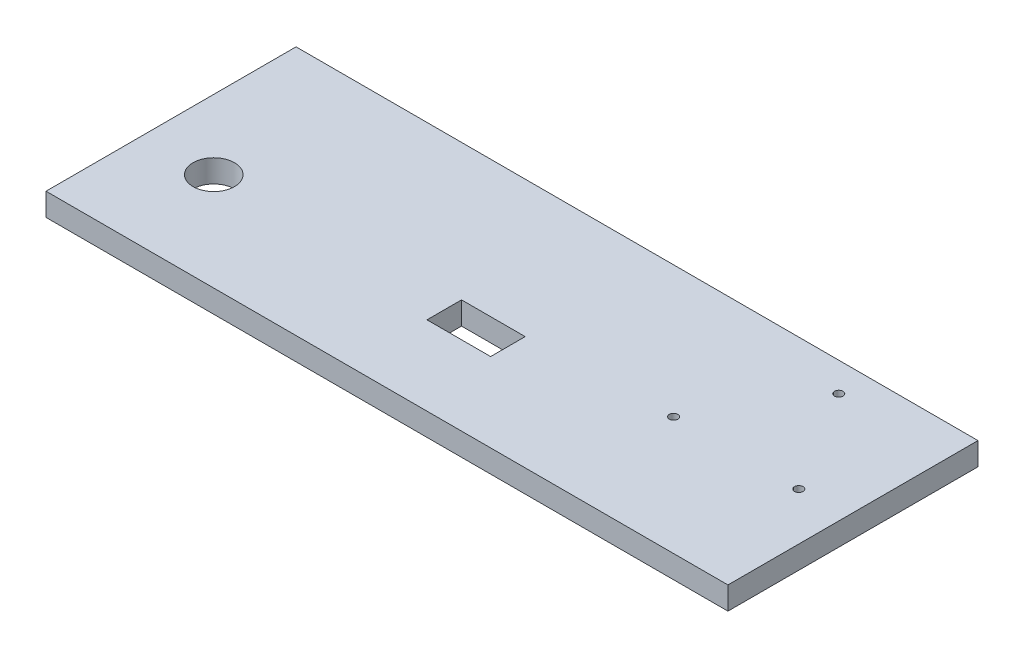
SolidWorks part; units mm, degrees
ref_plane "Front Plane" through (0, 0, 0) normal (0, 0, 1) x (1, 0, 0)
ref_plane "Top Plane" through (0, 0, 0) normal (0, 1, 0) x (1, 0, 0)
ref_plane "Right Plane" through (0, 0, 0) normal (1, 0, 0) x (0, 0, -1)
sketch "Sketch1" plane through (0, 0, 0) normal (0, 1, 0) x (1, 0, 0)
  line L1 (-47.625, -17.4625) -> (47.625, -17.4625)
  line L2 (-47.625, -17.4625) -> (-47.625, 17.4625)
  line L3 (-47.625, 17.4625) -> (47.625, 17.4625)
  line L4 (47.625, -17.4625) -> (47.625, 17.4625)
  line L5 (-47.625, -17.4625) -> (47.625, 17.4625) construction
  line L6 (-47.625, 17.4625) -> (47.625, -17.4625) construction
  point P0 (0, 0)
  dimension "D1" = 95.25
  dimension "D2" = 34.925
extrude "Boss-Extrude1" add sketch "Sketch1" along normal blind 3.175
hole_wizard "Tap Drill for #0-80 Tap1" positions "Sketch2" profile "Sketch3" hole size "#0-80" standard "ANSI Inch" end condition through all
sketch "Sketch2" plane through (0, 3.175, 0) normal (0, 1, 0) x (1, 0, 0)
  point P0 (40.9766, -0.9208)
  point P3 (23.4886, -0.9208)
  point P6 (32.2326, 13.4048)
sketch "Sketch3" plane through (40.9766, 3.175, 0.9208) normal (1, 0, 0) x (0, 0, 1)
  line L0 (0, 0) -> (0, 3.175)
  line L1 (0, 3.175) -> (0.5956, 3.175)
  line L2 (0.5956, 3.175) -> (0.5956, 0)
  line L5 (0.5956, 0) -> (0, 0)
  line L11 (0, -6.35) -> (0, 107.95) construction
  dimension "Thru Hole Dia." = 1.1913
  dimension "Thru Hole Depth" = 3.175
hole_wizard "#12 Clearance Hole1" positions "Sketch4" profile "Sketch5" hole size "#12" standard "ANSI Inch" end condition through all
sketch "Sketch4" plane through (0, 3.175, 0) normal (0, 1, 0) x (1, 0, 0)
  point P0 (-37.9095, -3.7465)
sketch "Sketch5" plane through (-37.9095, 3.175, 3.7465) normal (1, 0, 0) x (0, 0, 1)
  line L0 (0, 0) -> (0, 3.175)
  line L1 (0, 3.175) -> (2.8956, 3.175)
  line L2 (2.8956, 3.175) -> (2.8956, 0)
  line L5 (2.8956, 0) -> (0, 0)
  line L11 (0, -6.35) -> (0, 107.95) construction
  dimension "Thru Hole Dia." = 5.7912
  dimension "Thru Hole Depth" = 3.175
sketch "Sketch6" plane through (0, 3.175, 0) normal (0, 1, 0) x (1, 0, 0)
  line L1 (3.429, -6.4135) -> (-5.461, -6.4135)
  line L2 (3.429, -6.4135) -> (3.429, -1.5875)
  line L3 (3.429, -1.5875) -> (-5.461, -1.5875)
  line L4 (-5.461, -6.4135) -> (-5.461, -1.5875)
extrude "Cut-Extrude1" cut sketch "Sketch6" against normal through all
